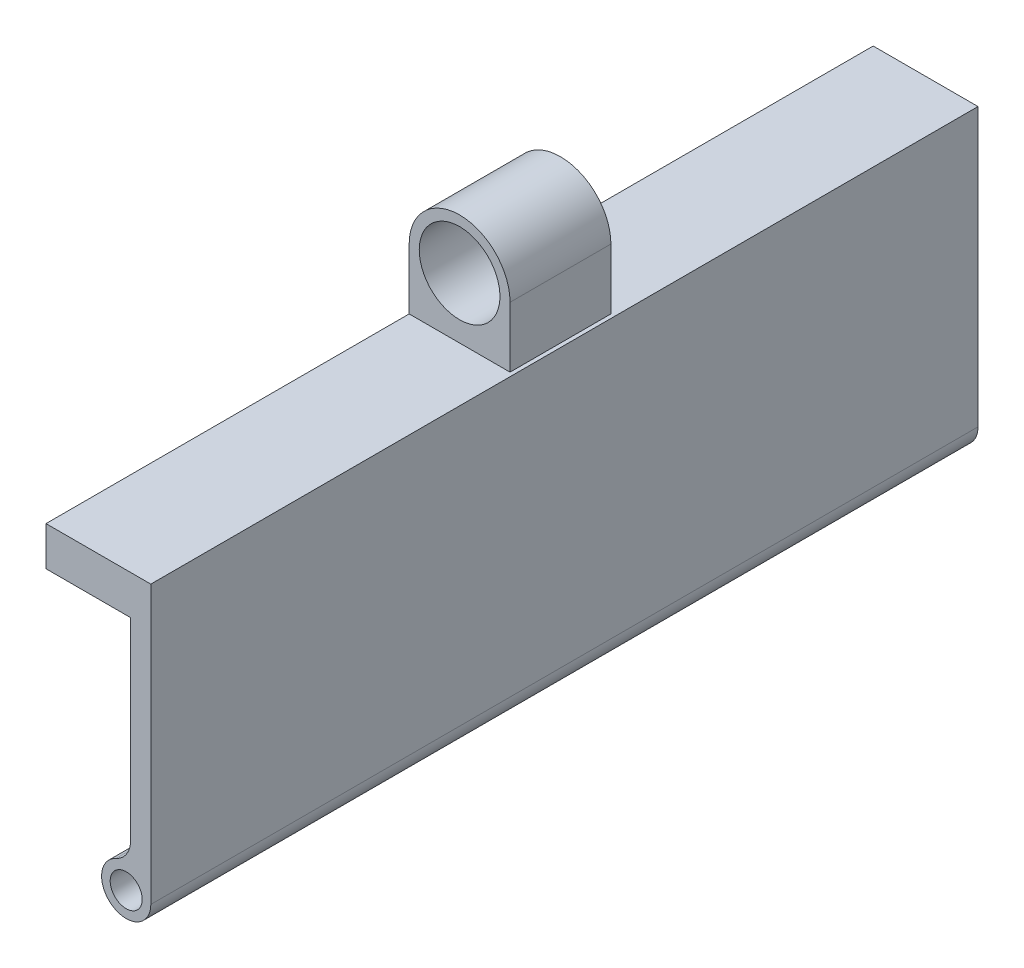
SolidWorks part; units mm, degrees
ref_plane "Front Plane" through (0, 0, 0) normal (0, 0, 1) x (1, 0, 0)
ref_plane "Top Plane" through (0, 0, 0) normal (0, 1, 0) x (1, 0, 0)
ref_plane "Right Plane" through (0, 0, 0) normal (1, 0, 0) x (0, 0, -1)
sketch "Sketch1" plane through (0, 0, 0) normal (0, 0, 1) x (1, 0, 0)
  line L0 (0, 0) -> (3.1723, 0) construction
  line L1 (2.44, 0) -> (2.44, 25)
  line L2 (0.44, 4.49) -> (0.44, 25)
  line L3 (0.44, 25) -> (2.44, 25)
  circle A0 centre (0, 0) radius 1.5875
  arc A1 (-1.0175, 2.2177) -> (2.44, 0) centre (0, 0) ccw
  arc A2 (0.44, 4.49) -> (-1.0175, 2.2177) centre (-2.06, 4.49) cw
  dimension "D1" = 3.175
  dimension "D2" = 4.88
  dimension "D5" = 2.5
  dimension "D3" = 25
  dimension "D4" = 2
extrude "Boss-Extrude1" add sketch "Sketch1" along normal blind 82
sketch "Sketch3" plane through (0, 25, 0) normal (0, 1, 0) x (1, 0, 0)
  line L1 (0.44, -82) -> (2.44, -82)
  line L2 (0.44, -82) -> (0.44, 0)
  line L3 (0.44, 0) -> (2.44, 0)
  line L4 (2.44, -82) -> (2.44, 0)
extrude "Boss-Extrude4" add sketch "Sketch3" along normal blind 2.5
sketch "Sketch6" plane through (0.44, 0, 0) normal (-1, 0, 0) x (0, 0, 1)
  line L1 (82, 27.5) -> (0, 27.5)
  line L2 (82, 27.5) -> (82, 23.6193)
  line L3 (82, 23.6193) -> (0, 23.6193)
  line L4 (0, 27.5) -> (0, 23.6193)
  dimension "D1" = 23.01
extrude "Boss-Extrude5" add sketch "Sketch6" along normal blind 8.39
ref_plane "Plane2" through (-7.95, 23.6193, 0) normal (0, 0, 1) x (1, 0, 0)
ref_plane "Plane3" through (-7.95, 23.6193, 82) normal (0, 0, 1) x (1, 0, 0)
ref_plane "Plane4" through (0.44, 23.6193, 82) normal (0, 0, 1) x (1, 0, 0)
sketch "Sketch8" plane through (0, 0, 0) normal (0, 0, -1) x (-1, 0, 0)
  line L0 (7.95, 27.5) -> (7.95, 33.5)
  line L1 (-2.05, 33.5) -> (-2.05, 27.5)
  line L2 (-2.44, 27.5) -> (7.95, 27.5) construction
  line L3 (7.95, 27.5) -> (-2.05, 27.5)
  circle A0 centre (2.95, 33.5) radius 4
  arc A1 (7.95, 33.5) -> (-2.05, 33.5) centre (2.95, 33.5) ccw
extrude "Boss-Extrude6" add sketch "Sketch8" against normal blind 10 from offset 36 offset against normal yes
sketch "Sketch10" plane through (0.44, 0, 0) normal (-1, 0, 0) x (0, 0, 1)
  line L1 (11.7203, 4.49) -> (23.4406, 4.49)
  line L2 (11.7203, 4.49) -> (11.7203, -2.44)
  line L3 (11.7203, -2.44) -> (23.4406, -2.44)
  line L4 (23.4406, 4.49) -> (23.4406, -2.44)
  line L5 (0, -2.44) -> (82, -2.44) construction
  line L6 (82, 4.49) -> (0, 4.49) construction
  dimension "D1" = 11.7203
  dimension "D2" = 11.7203
extrude "Cut-Extrude1" cut sketch "Sketch10" along normal blind 10
pattern_linear "LPattern1" count 3 spacing 23.4406 along (0, 0, 1) of "Cut-Extrude1"
